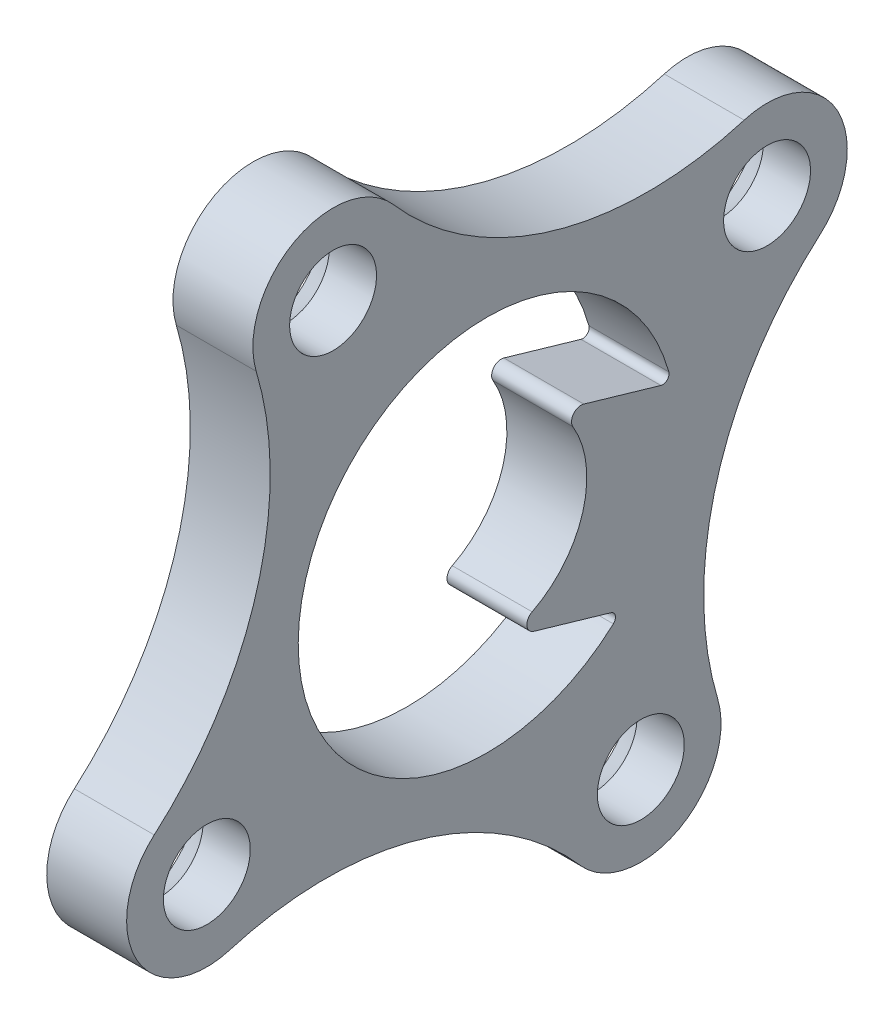
SolidWorks part; units mm, degrees
material "6061-T6 (SS)"
ref_plane "Front Plane" through (0, 0, 0) normal (0, 0, 1) x (1, 0, 0)
ref_plane "Top Plane" through (0, 0, 0) normal (0, 1, 0) x (1, 0, 0)
ref_plane "Right Plane" through (0, 0, 0) normal (1, 0, 0) x (0, 0, -1)
sketch "Sketch1" plane through (-52.0781, 0, 0) normal (-1, 0, 0) x (0, 0, 1)
  line L0 (-6.9114, 1.693) -> (-3.848, 2.5841)
  line L1 (-34.0142, 4.0065) -> (-35.1747, 4.0612) construction
  line L2 (-1.8616, -4.2449) -> (-4.925, -5.136)
  line L3 (-4.6961, -5.3339) -> (-0.0029, -3.9687) construction
  line L5 (-37.0563, -3.3999) -> (-36.7386, -3.3463) construction
  line L6 (6.1147, 11.1311) -> (-6.1147, -11.1311) construction
  line L7 (11.1311, -6.1147) -> (-11.1311, 6.1147) construction
  arc A0 (-3.848, 2.5841) -> (-3.4139, 2.0239) centre (-3.7416, 2.2182) cw
  arc A1 (-3.4139, 2.0239) -> (-1.7957, -3.5393) centre (0, 0) ccw
  arc A2 (-1.7957, -3.5393) -> (-1.8616, -4.2449) centre (-1.9681, -3.8791) cw
  arc A3 (-0.0029, -3.9687) -> (-2.1312, 3.348) centre (0, 0) ccw construction
  circle A4 centre (0, 0) radius 3.9687 construction
  arc A5 (-6.9114, 1.693) -> (-7.2271, 2.0048) centre (-6.9823, 1.9369) cw
  arc A6 (9.1698, 10.2214) -> (3.7082, 13.2217) centre (6.1147, 11.1311) ccw construction
  arc A7 (9.1698, 10.2214) -> (13.2217, -3.7082) centre (22.0034, 6.4003) ccw construction
  arc A8 (-7.2271, 2.0048) -> (-5.0242, -5.5684) centre (0, 0) cw
  arc A9 (-5.0242, -5.5684) -> (-4.925, -5.136) centre (-4.854, -5.3798) cw
  circle A12 centre (-11.1311, 6.1147) radius 3.175 construction
  circle A13 centre (-11.1311, 6.1147) radius 2.6924 construction
  circle A14 centre (0, 0) radius 9.525 construction
  arc A15 (10.2214, -9.1698) -> (13.2217, -3.7082) centre (11.1311, -6.1147) ccw construction
  arc A16 (10.2214, -9.1698) -> (-3.7082, -13.2217) centre (6.4003, -22.0034) ccw construction
  arc A17 (-9.1698, -10.2214) -> (-3.7082, -13.2217) centre (-6.1147, -11.1311) ccw construction
  arc A18 (-9.1698, -10.2214) -> (-13.2217, 3.7082) centre (-22.0034, -6.4003) ccw construction
  arc A19 (-10.2214, 9.1698) -> (-13.2217, 3.7082) centre (-11.1311, 6.1147) ccw construction
  arc A20 (-10.2214, 9.1698) -> (3.7082, 13.2217) centre (-6.4003, 22.0034) ccw construction
  arc A21 (9.1698, 10.2214) -> (3.7082, 13.2217) centre (6.1147, 11.1311) ccw
  arc A22 (9.1698, 10.2214) -> (13.2217, -3.7082) centre (22.0034, 6.4003) ccw
  arc A23 (10.2214, -9.1698) -> (13.2217, -3.7082) centre (11.1311, -6.1147) ccw
  arc A24 (10.2214, -9.1698) -> (-3.7082, -13.2217) centre (6.4003, -22.0034) ccw
  arc A25 (-9.1698, -10.2214) -> (-3.7082, -13.2217) centre (-6.1147, -11.1311) ccw
  arc A26 (-9.1698, -10.2214) -> (-13.2217, 3.7082) centre (-22.0034, -6.4003) ccw
  arc A27 (-10.2214, 9.1698) -> (-13.2217, 3.7082) centre (-11.1311, 6.1147) ccw
  arc A28 (-10.2214, 9.1698) -> (3.7082, 13.2217) centre (-6.4003, 22.0034) ccw
  arc A29 (-4.7873, -5.7733) -> (-7.1371, 2.3048) centre (0, 0) ccw construction
  dimension "D1" = 0.381
  dimension "D2" = 0.254
  dimension "D3" = 25.4
  dimension "D6" = 5.3848
  dimension "D7" = 19.05
  dimension "D5" = 45
  dimension "D8" = 7.112
extrude "Boss-Extrude1" add sketch "Sketch1" against normal blind 3.175
hole_wizard "CSK for #4 Flat Head Machine Screw1" positions "Sketch3" profile "Sketch4" countersink size "#4" standard "ANSI Inch" end condition up to next
sketch "Sketch3" plane through (-52.0781, 0, 0) normal (1, 0, 0) x (0, 0, -1)
  point P0 (11.1311, 6.1147)
  point P13 (-6.1147, 11.1311)
  point P16 (-11.1311, -6.1147)
  point P19 (6.1147, -11.1311)
sketch "Sketch4" plane through (-52.0781, 6.1147, -11.1311) normal (0, 1, 0) x (0, 0, 1)
  line L0 (0, 0) -> (0, 3.175)
  line L1 (0, 3.175) -> (1.7272, 3.175)
  line L2 (1.7272, 3.175) -> (1.7272, 1.3003)
  line L3 (1.7272, 1.3003) -> (2.8575, 0)
  line L5 (2.8575, 0) -> (0, 0)
  line L6 (-1.7272, 1.3003) -> (-2.8575, 0) construction
  line L11 (0, -6.35) -> (0, 107.95) construction
  dimension "Thru Hole Dia." = 3.4544
  dimension "Thru Hole Depth" = 3.175
  dimension "Near C'Sink Dia." = 5.715
  dimension "Near C'Sink Angle" = 82
